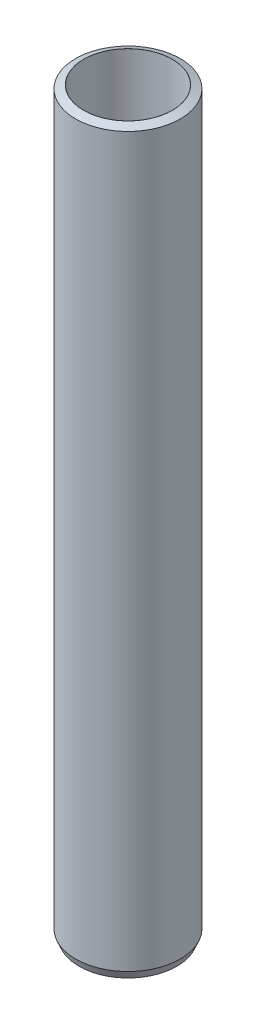
SolidWorks part; units mm, degrees
ref_plane "Front Plane" through (0, 0, 0) normal (0, 0, 1) x (1, 0, 0)
ref_plane "Top Plane" through (0, 0, 0) normal (0, 1, 0) x (1, 0, 0)
ref_plane "Right Plane" through (0, 0, 0) normal (1, 0, 0) x (0, 0, -1)
sketch "Sketch1" plane through (0, 0, 0) normal (0, 1, 0) x (1, 0, 0)
  circle A0 centre (0, 0) radius 42.5
  dimension "SHAFT_OD" = 85
extrude "Boss-Extrude1" add sketch "Sketch1" along normal blind 600
sketch "Sketch2" plane through (0, 0, 0) normal (0, 1, 0) x (1, 0, 0)
  circle A0 centre (0, 0) radius 35.9272
  dimension "BORE_D" = 71.8543
extrude "Cut-Extrude1" cut sketch "Sketch2" along normal through all
chamfer "Chamfer1" distance 2.7639 angle 66.991 2 edges at (0, 600, 42.5) (0, 0, 42.5) first distance on face at (0, 600, 42.5) first distance on face at (0, 0, 35.9272)
